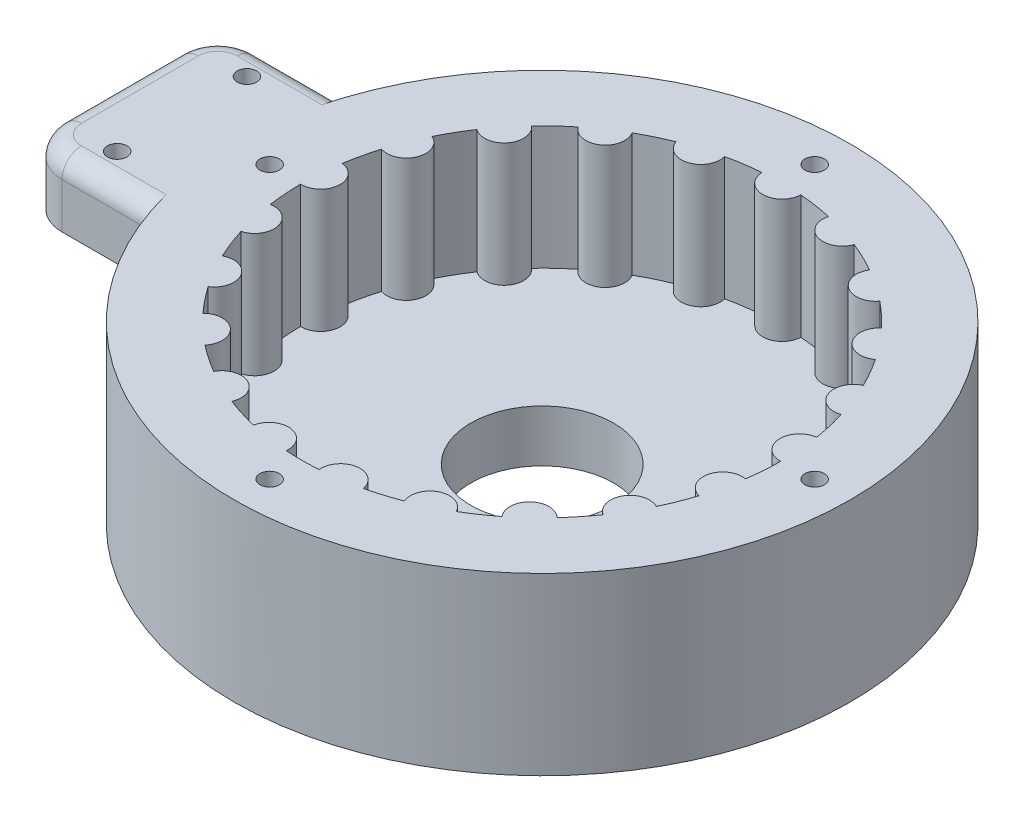
SolidWorks part; units mm, degrees
ref_plane "Front Plane" through (0, 0, 0) normal (0, 0, 1) x (1, 0, 0)
ref_plane "Top Plane" through (0, 0, 0) normal (0, 1, 0) x (1, 0, 0)
ref_plane "Right Plane" through (0, 0, 0) normal (1, 0, 0) x (0, 0, -1)
sketch "Sketch1" plane through (0, 0, 0) normal (0, 1, 0) x (1, 0, 0)
  circle A0 centre (0, 0) radius 37
  circle A1 centre (0, 37) radius 3
  circle A2 centre (10.9059, 35.3562) radius 3
  circle A3 centre (20.8428, 30.5708) radius 3
  circle A4 centre (28.9278, 23.0691) radius 3
  circle A5 centre (34.4423, 13.5176) radius 3
  circle A6 centre (36.8965, 2.765) radius 3
  circle A7 centre (36.0723, -8.2333) radius 3
  circle A8 centre (32.0429, -18.5) radius 3
  circle A9 centre (25.1664, -27.1229) radius 3
  circle A10 centre (16.0537, -33.3358) radius 3
  circle A11 centre (5.5146, -36.5867) radius 3
  circle A12 centre (-5.5146, -36.5867) radius 3
  circle A13 centre (-16.0537, -33.3358) radius 3
  circle A14 centre (-25.1664, -27.1229) radius 3
  circle A15 centre (-32.0429, -18.5) radius 3
  circle A16 centre (-36.0723, -8.2333) radius 3
  circle A17 centre (-36.8965, 2.765) radius 3
  circle A18 centre (-34.4423, 13.5176) radius 3
  circle A19 centre (-28.9278, 23.0691) radius 3
  circle A20 centre (-20.8428, 30.5708) radius 3
  circle A21 centre (-10.9059, 35.3562) radius 3
  circle A27 centre (0, 0) radius 47.5
  point P57 (0, 0)
  point P97 (0, 0)
  dimension "D1" = 74
  dimension "D2" = 21
  dimension "D3" = 95
extrude "Boss-Extrude1" add sketch "Sketch1" along normal blind 27 contours A27 A0 A1 A2 A3 A4 A5 A6 A7 A8 A9 A10 A11 A12 A13 A14 A15 A16 A17 A18 A19 A20 A21 | A13 | A12 | A14 | A15 | A16 | A17 | A18 | A19 | A20 | A21 | A1 | A2 | A3 | A4 | A5 | A6 | A7 | A8 | A9 | A10 | A11 region at (-46.1565, 0, 0)
sketch "Sketch2" plane through (0, 0, 0) normal (0, -1, 0) x (1, 0, 0)
  circle A0 centre (0, 0) radius 38
  circle A1 centre (0, 0) radius 11
  dimension "D1" = 76
  dimension "D2" = 22
extrude "Boss-Extrude2" add sketch "Sketch2" against normal blind 8
sketch "Sketch4" plane through (0, 8, 0) normal (0, 1, 0) x (1, 0, 0)
  line L0 (-11, 0) -> (11, 0) construction
  circle A0 centre (0, 12.5) radius 1.25
  circle A1 centre (0, 0) radius 11 construction
  circle A2 centre (0, -12.5) radius 1.25
  dimension "D1" = 12.5
sketch "Sketch5" plane through (0, 27, 0) normal (0, 1, 0) x (1, 0, 0)
  circle A0 centre (0, 42) radius 1.5
  circle A1 centre (42, 0) radius 1.5
  circle A2 centre (0, -42) radius 1.5
  circle A3 centre (-42, 0) radius 1.5
  point P12 (0, 0)
  dimension "D1" = 42
  dimension "D3" = 3
  dimension "D2" = 4
extrude "Cut-Extrude2" cut sketch "Sketch5" against normal blind 10 contours A0 | A3 | A2 | A1
ref_plane "Plane1" through (0, 27, 0) normal (0, 1, 0) x (1, 0, 0)
sketch "Sketch9" plane through (0, 27, 0) normal (0, 1, 0) x (1, 0, 0)
  line L0 (-43.5, 0) -> (-43.5, 15)
  line L1 (-43.5, 15) -> (-65, 15)
  line L3 (-65, 15) -> (-65, -15)
  line L4 (-65, -15) -> (-43.5, -15)
  line L5 (-43.5, -15) -> (-43.5, 0)
  circle A0 centre (-42, 0) radius 1.5 construction
  circle A1 centre (-42, 0) radius 1.5 construction
  dimension "D1" = 15
  dimension "D2" = 21.5
  dimension "D3" = 21.5
extrude "Boss-Extrude3" add sketch "Sketch9" against normal blind 10 contours L4 L5 L0 L1 L3
sketch "Sketch10" plane through (0, 27, 0) normal (0, 1, 0) x (1, 0, 0)
  line L0 (-65, -15) -> (-45.0694, -15) construction
  line L1 (-45.0694, 15) -> (-65, 15) construction
  line L2 (-65, 15) -> (-65, -15) construction
  circle A0 centre (-55.5, 10) radius 1.5
  circle A1 centre (-55.5, -10) radius 1.5
  dimension "D1" = 5
  dimension "D5" = 3
  dimension "D6" = 3
  dimension "D2" = 5
  dimension "D3" = 9.5
  dimension "D4" = 9.5
extrude "Cut-Extrude3" cut sketch "Sketch10" against normal blind 10
fillet "Fillet2" radius 3 3 edges at (-55.0347, 27, -15) (-65, 27, 0) (-55.0347, 27, 15)
fillet "Fillet3" radius 6 4 edges at (-64.1213, 26.1213, 14.1213) (-64.1213, 26.1213, -14.1213) (-65, 20.5, -15) (-65, 20.5, 15)
